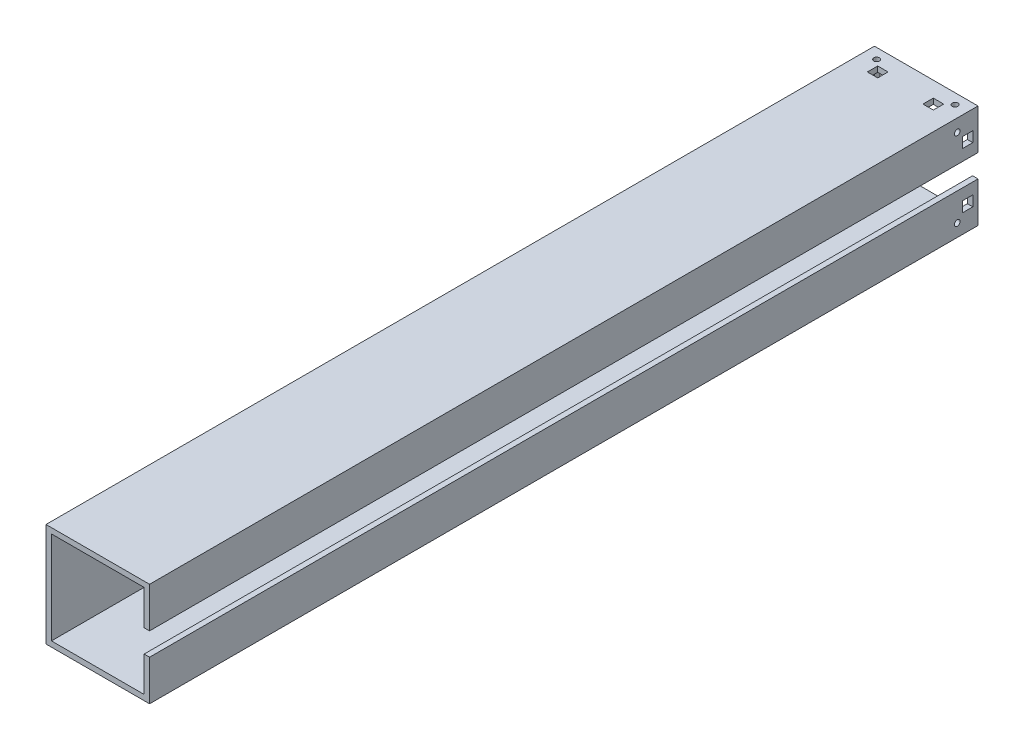
SolidWorks part; units mm, degrees
ref_plane "Front Plane" through (0, 0, 0) normal (1, 0, 0) x (0, 1, 0)
ref_plane "Top Plane" through (0, 0, 0) normal (0, 0, 1) x (0, 1, 0)
ref_plane "Right Plane" through (0, 0, 0) normal (0, 1, 0) x (-1, 0, 0)
sketch "Sketch1" plane through (0, 0, 0) normal (0, 0, 1) x (0, 1, 0)
  line L0 (28.4162, -28.4162) -> (28.4162, 28.4162)
  line L1 (31.75, -31.75) -> (-31.75, -31.75)
  line L2 (31.75, -31.75) -> (31.75, 31.75)
  line L3 (31.75, 31.75) -> (-31.75, 31.75)
  line L4 (-31.75, -31.75) -> (-31.75, 31.75)
  line L5 (31.75, -31.75) -> (-31.75, 31.75) construction
  line L6 (31.75, 31.75) -> (-31.75, -31.75) construction
  line L7 (28.4162, 28.4162) -> (-28.4162, 28.4162)
  line L8 (-28.4162, -28.4162) -> (-28.4162, 28.4162)
  line L9 (28.4162, -28.4162) -> (-28.4162, -28.4162)
  line L11 (6.985, -31.75) -> (-6.985, -31.75)
  line L12 (6.985, -31.75) -> (6.985, -28.4163)
  line L13 (6.985, -28.4163) -> (-6.985, -28.4163)
  line L14 (-6.985, -31.75) -> (-6.985, -28.4163)
  line L15 (6.985, -31.75) -> (-6.985, -28.4163) construction
  line L16 (6.985, -28.4163) -> (-6.985, -31.75) construction
  point P0 (0, 0)
  point P10 (0, -30.0831)
  dimension "D1" = 63.5
  dimension "D3" = 13.97
  dimension "D2" = 56.8325
extrude "Boss-Extrude1" add sketch "Sketch1" along normal blind 508 contours L1 L14 L9 L8 L7 L0 L12 L2 L3 L4 region at (0, 29.3143, 0)
sketch "Sketch2" plane through (0, 0, 0) normal (0, 1, 0) x (-1, 0, 0)
  line L0 (-28.4162, 0) -> (28.4162, 0) construction
  line L1 (-28.4162, 0) -> (28.4162, 0) construction
  line L2 (0, 0) -> (0, 508) construction
  line L3 (-31.75, 508) -> (31.75, 508) construction
  line L5 (22.225, 6.35) -> (-22.225, 6.35) construction
  line L6 (22.225, 6.35) -> (22.225, 19.05) construction
  line L7 (22.225, 19.05) -> (-22.225, 19.05) construction
  line L8 (-22.225, 6.35) -> (-22.225, 19.05) construction
  line L9 (22.225, 6.35) -> (-22.225, 19.05) construction
  line L10 (22.225, 19.05) -> (-22.225, 6.35) construction
  circle A3 centre (-22.225, 19.05) radius 1.75 construction
  circle A4 centre (22.225, 19.05) radius 1.75 construction
  circle A5 centre (22.225, 6.35) radius 1.75 construction
  circle A6 centre (-22.225, 6.35) radius 1.75 construction
  circle A7 centre (-24.05, 6.35) radius 1.75
  circle A8 centre (24.05, 6.35) radius 1.75
  point P2 (0, 12.7)
  dimension "D1" = 3.5
  dimension "D2" = 6.35
  dimension "D6" = 6.35
  dimension "D3" = 12.7
  dimension "D4" = 44.45
  dimension "D5" = 24.05
extrude "Cut-Extrude1" cut sketch "Sketch2" against normal blind 254 and the other way blind 254
sketch "Sketch4" plane through (31.75, 0, 0) normal (1, 0, 0) x (0, 1, 0)
  line L0 (-28.4162, 508) -> (-28.4162, 0) construction
  line L1 (-28.4162, 508) -> (-28.4162, 0) construction
  line L2 (-6.985, 0) -> (-31.75, 0) construction
  line L3 (0, 0) -> (0, 508) construction
  line L4 (-6.985, 508) -> (-31.75, 508) construction
  line L5 (31.75, 0) -> (6.985, 0) construction
  circle A1 centre (-22.225, 25.4) radius 1.75 construction
  circle A3 centre (-12.7, 12.7) radius 1.75 construction
  circle A6 centre (12.7, 12.7) radius 1.75 construction
  circle A7 centre (22.225, 25.4) radius 1.75 construction
  circle A8 centre (24.05, 12.7) radius 1.75
  circle A9 centre (-24.05, 12.7) radius 1.75
  dimension "D1" = 22.225
  dimension "D2" = 3.5
  dimension "D4" = 12.7
  dimension "D6" = 24.05
  dimension "D7" = 3.5
  dimension "D3" = 25.4
  dimension "D5" = 12.7
  dimension "D8" = 12.7
extrude "Cut-Extrude2" cut sketch "Sketch4" against normal blind 254
sketch "Sketch6" plane through (31.75, 0, 0) normal (1, 0, 0) x (0, 1, 0)
  line L0 (31.75, 4.6) -> (31.75, 8.1) construction
  line L5 (31.75, 4.6) -> (31.75, 8.1) construction
  line L6 (0, 0) -> (0, 9.525) construction
  line L7 (15.05, 11.35) -> (19.05, 11.35) construction
  line L8 (15.05, 11.35) -> (15.05, 1.35) construction
  line L9 (15.05, 1.35) -> (19.05, 1.35) construction
  line L10 (19.05, 11.35) -> (19.05, 1.35) construction
  line L11 (13.875, 9.525) -> (20.225, 9.525)
  line L12 (13.875, 9.525) -> (13.875, 3.175)
  line L13 (13.875, 3.175) -> (20.225, 3.175)
  line L14 (20.225, 9.525) -> (20.225, 3.175)
  line L15 (28.4163, 0) -> (-28.4162, 0) construction
  line L16 (-13.875, 3.175) -> (-20.225, 3.175)
  line L17 (-20.225, 9.525) -> (-20.225, 3.175)
  line L18 (-13.875, 9.525) -> (-20.225, 9.525)
  line L19 (-13.875, 9.525) -> (-13.875, 3.175)
  point P3 (0, 0)
  point P7 (31.75, 6.35)
  point P9 (19.05, 6.35)
  point P11 (17.05, 11.35)
  point P12 (20.225, 6.35)
  point P17 (17.05, 9.525)
  dimension "D1" = 10
  dimension "D2" = 4
  dimension "D3" = 19.05
  dimension "D4" = 6.35
  dimension "D5" = 6.35
extrude "Cut-Extrude4" cut sketch "Sketch6" against normal blind 90.678
sketch "Sketch7" plane through (0, 31.75, 0) normal (0, 1, 0) x (-1, 0, 0)
  line L0 (-31.75, 14.45) -> (-31.75, 10.95) construction
  line L1 (-31.75, 14.45) -> (-31.75, 10.95)
  line L2 (0, 0) -> (0, 15.875) construction
  line L3 (-19.05, 17.7) -> (-15.05, 17.7) construction
  line L4 (-19.05, 17.7) -> (-19.05, 7.7) construction
  line L5 (-19.05, 7.7) -> (-15.05, 7.7) construction
  line L6 (-15.05, 17.7) -> (-15.05, 7.7) construction
  line L7 (-20.225, 15.875) -> (-13.875, 15.875)
  line L8 (-20.225, 15.875) -> (-20.225, 9.525)
  line L9 (-20.225, 9.525) -> (-13.875, 9.525)
  line L10 (-13.875, 15.875) -> (-13.875, 9.525)
  line L11 (-31.75, 0) -> (31.75, 0) construction
  line L12 (20.225, 9.525) -> (13.875, 9.525)
  line L13 (13.875, 15.875) -> (13.875, 9.525)
  line L14 (20.225, 15.875) -> (13.875, 15.875)
  line L15 (20.225, 15.875) -> (20.225, 9.525)
  point P6 (-31.75, 12.7)
  point P7 (-19.05, 12.7)
  point P10 (-17.05, 17.7)
  point P14 (-20.225, 12.7)
  point P15 (-17.05, 15.875)
  dimension "D1" = 10
  dimension "D2" = 4
  dimension "D3" = 19.05
  dimension "D4" = 6.35
extrude "Cut-Extrude5" cut sketch "Sketch7" against normal blind 122.174 contours L10 L7 L8 L9 | L15 L14 L13 L12 region at (17.05, 31.75, 12.7) region at (-17.05, 31.75, 12.7)
